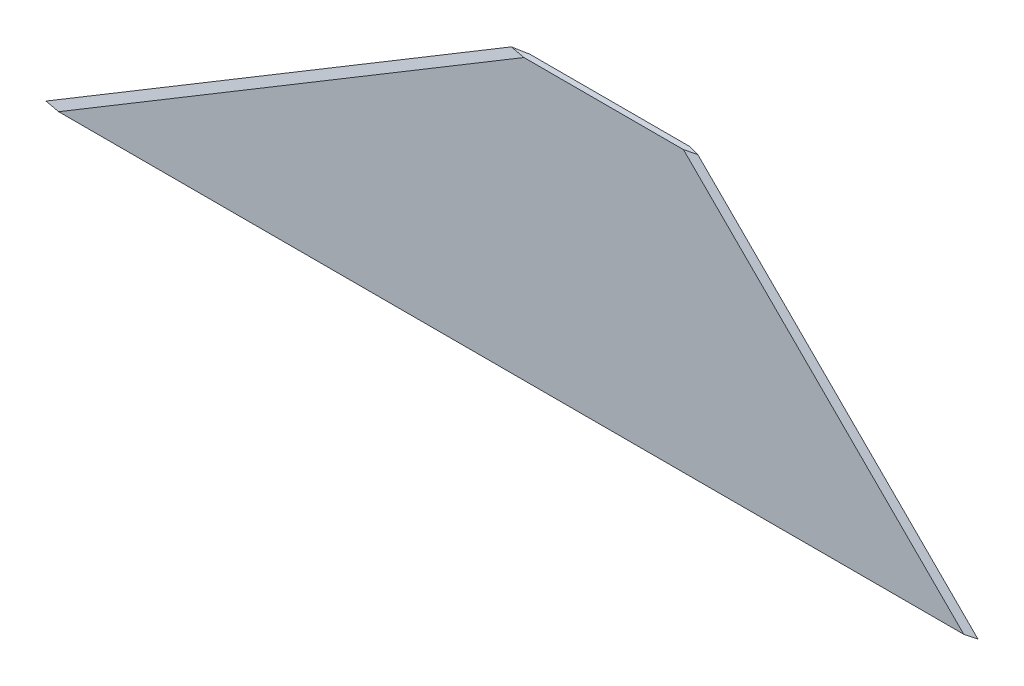
SolidWorks part; units mm, degrees
ref_plane "Front Plane" through (0, 0, 0) normal (0, 0, 1) x (1, 0, 0)
ref_plane "Top Plane" through (0, 0, 0) normal (0, 1, 0) x (1, 0, 0)
ref_plane "Right Plane" through (0, 0, 0) normal (1, 0, 0) x (0, 0, -1)
sketch "Sketch1" plane through (0, 0, 0) normal (0, 0, 1) x (1, 0, 0)
  line L0 (-508, 0) -> (0, 0)
  line L1 (0, 0) -> (-152.7638, 152.4)
  line L2 (-152.7638, 152.4) -> (-254.3638, 152.4)
  line L3 (-254.3638, 152.4) -> (-508, 0)
  line L4 (-508, 0) -> (-508, 192.899)
  line L5 (-244.5005, 152.4) -> (-498.1367, 0) construction
  line L6 (-159.9566, 152.4) -> (-7.1928, 0) construction
  line L7 (-108.3671, 70.5259) -> (-67.164, 29.421) construction
  line L11 (-203.5638, 152.4) -> (-203.5638, 0) construction
  line L17 (-281.9502, 111.5837) -> (-363.4644, 62.605) construction
  line L18 (23.1971, 30.48) -> (-21.4673, 30.48) construction
  line L19 (-43.2082, 121.92) -> (-102.5864, 121.92) construction
  point P23 (-203.5638, 152.4)
  point P30 (-7.1928, 0)
  point P32 (-37.6728, 0)
  point P33 (-498.1367, 0)
  point P35 (-467.6567, 0)
  dimension "D1" = 508
  dimension "D2" = 101.6
  dimension "D3" = 152.4
  dimension "D4" = 59
  dimension "D5" = 5.08
  dimension "D6" = 5.08
  dimension "D7" = 30.48
  dimension "D8" = 30.48
  dimension "D9" = 30.48
  dimension "D10" = 30.48
extrude "Boss-Extrude4" add sketch "Sketch1" along normal blind 3.175
chamfer "Chamfer1" distance 1.5875 angle 70 2 edges at (-381.1819, 76.2, 0) (-76.3819, 76.2, 0) first distance on face at (-381.1819, 76.2, 1.5875) first distance on face at (-76.3819, 76.2, 1.5875)
chamfer "Chamfer2" distance 1.5875 angle 70 2 edges at (-76.3819, 76.2, 3.175) (-381.1819, 76.2, 3.175) first distance on face at (-76.3819, 76.2, 2.3812) first distance on face at (-381.1819, 76.2, 2.3812)
